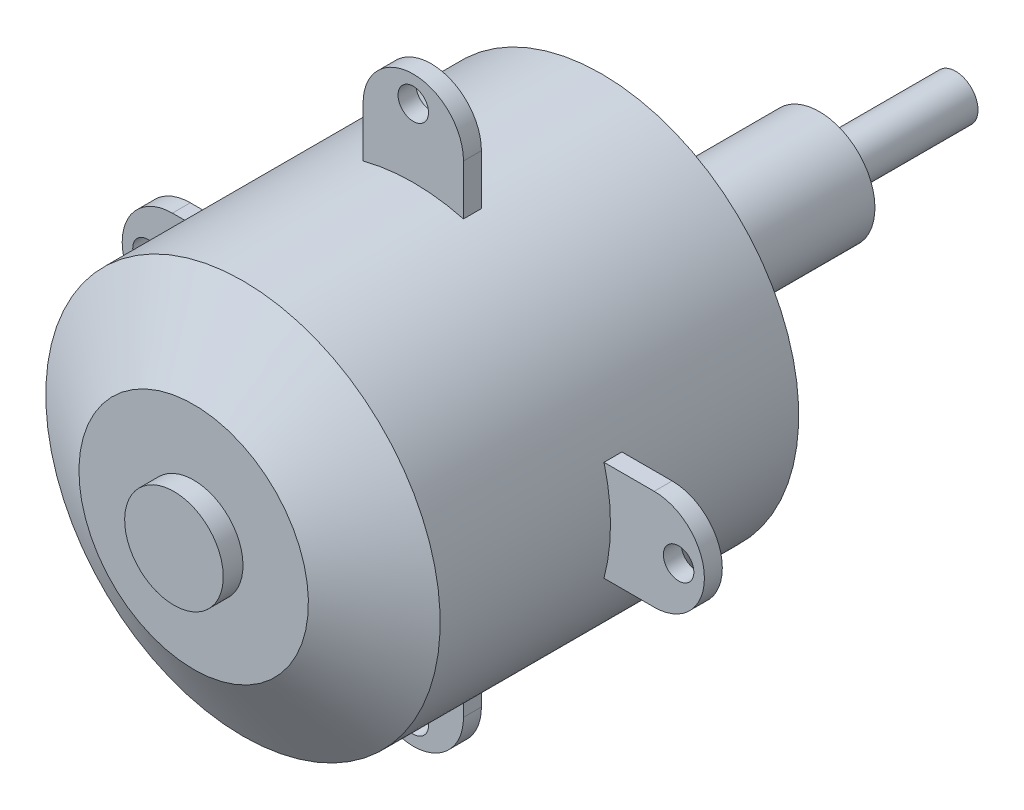
SolidWorks part; units mm, degrees
ref_plane "Front Plane" through (0, 0, 0) normal (0, 0, 1) x (1, 0, 0)
ref_plane "Top Plane" through (0, 0, 0) normal (0, 1, 0) x (1, 0, 0)
ref_plane "Right Plane" through (0, 0, 0) normal (1, 0, 0) x (0, 0, -1)
sketch "Sketch2" plane through (0, 0, 0) normal (1, 0, 0) x (0, 0, -1)
  line L0 (0, -1000) -> (0, 49000) construction
  line L1 (-16.1925, 0) -> (16.1925, 0)
  line L2 (-16.1925, 3.4925) -> (-16.1925, 8.128)
  line L3 (-12.7, 13.97) -> (12.7, 13.97)
  line L4 (16.1925, 0) -> (16.1925, 8.128) construction
  line L5 (-16.1925, 8.128) -> (-12.7, 13.97)
  line L6 (16.1925, 8.128) -> (12.7, 13.97)
  line L7 (16.1925, 3.937) -> (16.1925, 8.128)
  line L8 (-16.1925, 0) -> (-17.5895, 0)
  line L9 (16.1925, 0) -> (28.1305, 0)
  line L10 (-16.1925, 3.4925) -> (-17.5895, 3.4925)
  line L11 (-17.5895, 0) -> (-17.5895, 3.4925)
  line L12 (16.1925, 0) -> (16.1925, 3.937)
  line L13 (16.1925, 3.937) -> (28.1305, 3.937)
  line L14 (28.1305, 0) -> (28.1305, 3.937)
  line L16 (28.1305, 0) -> (37.7825, 0)
  line L17 (28.1305, 0) -> (28.1305, 1.5875)
  line L18 (28.1305, 1.5875) -> (37.7825, 1.5875)
  line L19 (37.7825, 0) -> (37.7825, 1.5875)
  point P4 (0, 0)
  point P6 (-16.1925, 8.128)
  point P8 (-12.7, 13.97)
  dimension "D1" = 32.385
  dimension "D2" = 13.97
  dimension "D3" = 8.128
  dimension "D4" = 12.7
  dimension "D5" = 3.4925
  dimension "D6" = 1.397
  dimension "D7" = 3.937
  dimension "D8" = 11.938
  dimension "D9" = 9.652
  dimension "D10" = 1.5875
revolve "Revolve1" add sketch "Sketch2" angle 360 about L1 region at (0, 6.6912, 0.1886) region at (0, 1.9685, -22.1615) region at (0, 0.7938, -32.9565)
ref_axis "Axis1" through (0, 0, -12.7) along (0, 0, 1)
sketch "Sketch3" plane through (0, 0, 0) normal (0, 0, 1) x (1, 0, 0)
  line L0 (-3.556, 13.5098) -> (3.556, 13.5098) construction
  line L1 (-3.556, 13.5098) -> (-3.556, 20.6218)
  line L2 (3.556, 13.5098) -> (3.556, 20.6218)
  line L3 (-3.556, 20.6218) -> (3.556, 20.6218)
  line L4 (0, -1000) -> (0, 49000) construction
  circle A0 centre (0, 0) radius 13.97 construction
  arc A1 (0, -13.97) -> (-3.556, 13.5098) centre (0, 0) ccw
  circle A2 centre (0, 18.796) radius 1.0795
  arc A3 (3.556, 17.0658) -> (-3.556, 17.0658) centre (0, 17.0658) ccw
  point P7 (0, 20.6218)
  point P16 (0, 13.97)
  dimension "D3" = 2.159
  dimension "D1" = 7.112
  dimension "D2" = 7.112
  dimension "D4" = 4.826
extrude "Boss-Extrude2" add sketch "Sketch3" along normal blind 0.635 and the other way blind 0.635 contours L2 A3 L1 A1 A2 region at (0, 16.7111, 0)
pattern_circular "CirPattern1" count 4 over 360 about axis through (0, 0, -12.7) along (0, 0, 1) of "Boss-Extrude2"
sketch "Sketch4" plane through (0, 0, 0) normal (0, 0, 1) x (1, 0, 0)
  line L0 (0, 18.796) -> (0, -18.796) construction
  line L1 (18.796, 0) -> (-18.796, 0) construction
